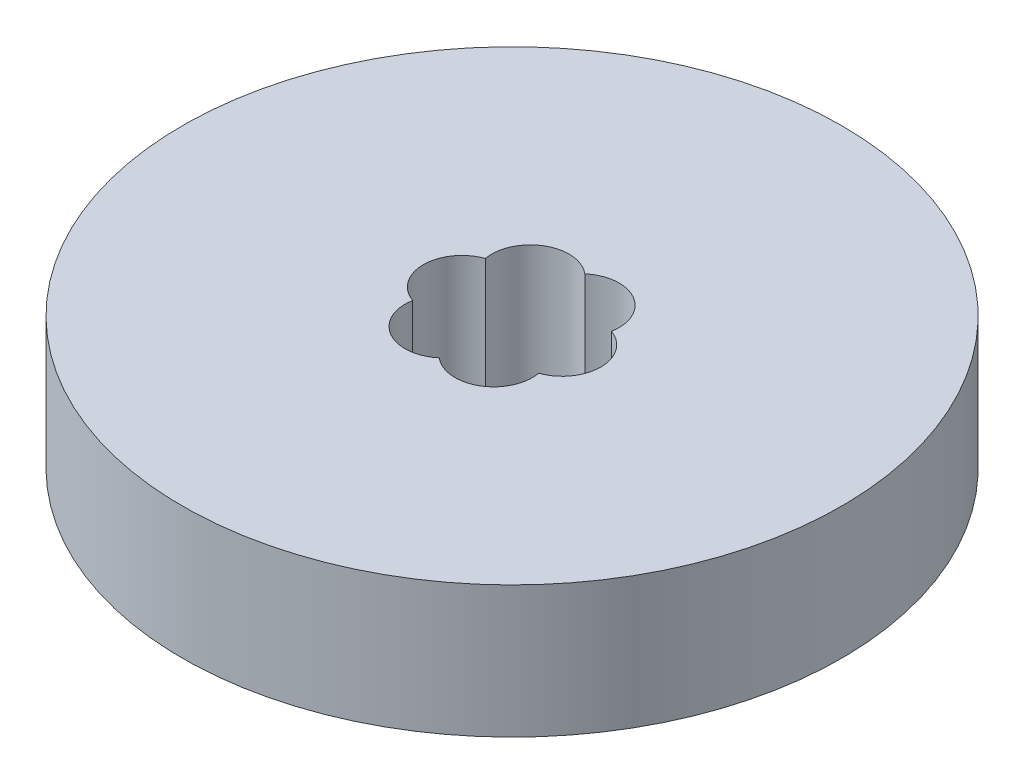
SolidWorks part; units mm, degrees
ref_plane "Front Plane" through (0, 0, 0) normal (0, 0, 1) x (1, 0, 0)
ref_plane "Top Plane" through (0, 0, 0) normal (0, 1, 0) x (1, 0, 0)
ref_plane "Right Plane" through (0, 0, 0) normal (1, 0, 0) x (0, 0, -1)
sketch "Sketch1" plane through (0, 0, 0) normal (0, 1, 0) x (1, 0, 0)
  circle A0 centre (0, 0) radius 32.5
  dimension "FLANGE_OD" = 65
extrude "Boss-Extrude1" add sketch "Sketch1" along normal blind 13
sketch "Sketch2" plane through (0, 0, 0) normal (0, 1, 0) x (1, 0, 0)
  circle A0 centre (0, 0) radius 5
  dimension "BORE_D" = 10
extrude "Cut-Extrude1" cut sketch "Sketch2" along normal through all
sketch "Sketch3" plane through (0, 13, 0) normal (0, 1, 0) x (1, 0, 0)
  circle A0 centre (0, 0) radius 4.9415 construction
  circle A1 centre (-4.9415, 0) radius 3.8081
  dimension "BOLT_D" = 7.6161
  dimension "BOLT_PCD" = 9.883
extrude "Cut-Extrude2" cut sketch "Sketch3" against normal blind 12.8474
pattern_circular "CirPattern1" count 6 over 360 about axis through (0, 0, 0) along (0, 1, 0) of "Cut-Extrude2"
